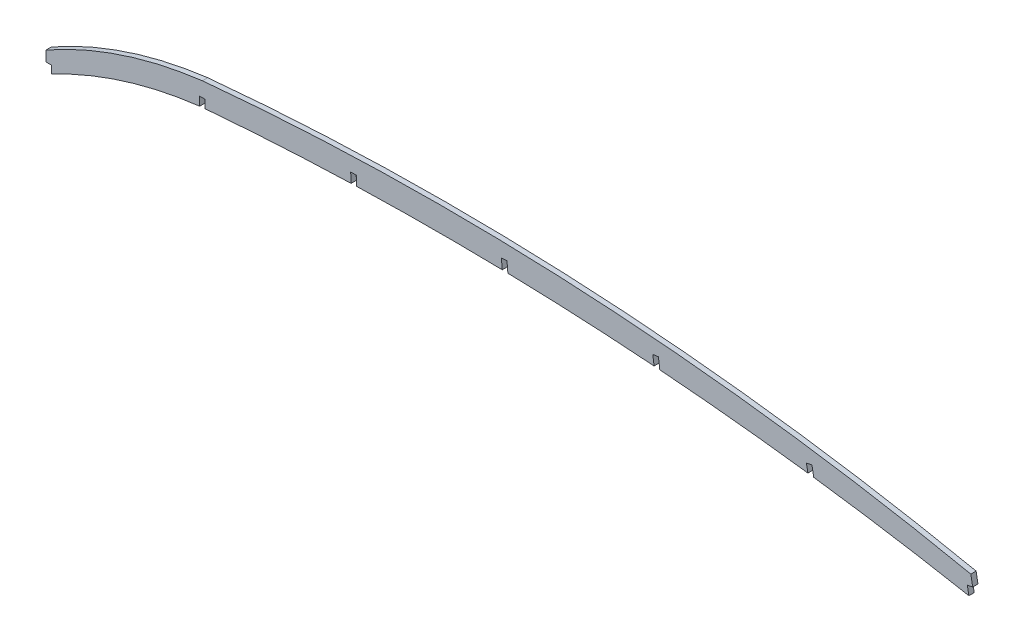
SolidWorks part; units mm, degrees
material "Balsa"
ref_plane "Front Plane" through (0, 0, 0) normal (0, 0, 1) x (1, 0, 0)
ref_plane "Top Plane" through (0, 0, 0) normal (0, 1, 0) x (1, 0, 0)
ref_plane "Right Plane" through (0, 0, 0) normal (1, 0, 0) x (0, 0, -1)
sketch "Sketch1" plane through (0, 0, 0) normal (0, 0, 1) x (1, 0, 0)
  line L2 (0, 0) -> (0, 169.3685) construction
  line L4 (93.98, 106.68) -> (556.5761, 106.68) construction
  line L9 (0, 106.68) -> (93.98, 106.68) construction
  line L14 (555.6382, 111.8229) -> (555.6382, 106.68) construction
  line L17 (555.6382, 111.8229) -> (557.917, 99.3265)
  line L19 (0, 106.68) -> (0, 93.98)
  line L20 (93.98, 137.668) -> (93.98, 123.7947) construction
  arc A6 (0, 106.68) -> (93.98, 137.668) centre (125.0054, -114.43) cw
  arc A8 (93.98, 137.668) -> (555.6382, 111.8229) centre (239.5165, -1398.7972) cw
  arc A9 (0, 93.98) -> (93.98, 123.7947) centre (122.3372, -128.6174) cw
  arc A25 (93.98, 123.7947) -> (557.917, 99.3265) centre (236.8486, -1577.8511) cw
  dimension "D4" = 254
  dimension "D2" = 93.98
  dimension "D8" = 1543.3426
  dimension "D9" = 100.334
  dimension "D3" = 30.988
  dimension "D12" = 254
  dimension "D14" = 1707.6328
  dimension "D1" = 106.68
  dimension "D5" = 462.5961
  dimension "D6" = 0.9378
  dimension "D7" = 5.1429
  dimension "D10" = 12.7025
  dimension "D11" = 12.7
  dimension "D13" = 13.8733
extrude "Boss-Extrude1" add sketch "Sketch1" along normal blind 3.175 contours A9 A25 L17 A8 A6 L19 region at (551.2665, 104.5698, 0)
sketch "Sketch2" plane through (0, 0, 3.175) normal (0, 0, 1) x (1, 0, 0)
  line L0 (0, 0) -> (0, 93.98) construction
  line L1 (0, 0) -> (93.98, 0) construction
  line L2 (93.98, 0) -> (93.98, 128.7725) construction
  line L3 (93.98, 0) -> (190.373, 0) construction
  line L4 (0, 93.98) -> (3.3528, 93.98)
  line L5 (0, 93.98) -> (0, 100.457)
  line L6 (0, 100.457) -> (3.3528, 100.457)
  line L7 (3.3528, 93.98) -> (3.3528, 100.457)
  line L8 (92.2909, 128.8487) -> (95.6691, 128.8487)
  line L9 (92.2909, 128.8487) -> (92.2909, 116.1487)
  line L10 (92.2909, 116.1487) -> (95.6691, 116.1487)
  line L11 (95.6691, 128.8487) -> (95.6691, 116.1487)
  line L12 (190.373, 0) -> (184.7454, 134.6815) construction
  line L13 (383.6414, 0) -> (367.0519, 124.8106) construction
  line L14 (367.0519, 124.8106) -> (366.2623, 130.7507) construction
  line L15 (183.0546, 134.6871) -> (186.4298, 134.8282)
  line L16 (183.0546, 134.6871) -> (183.5848, 121.9982)
  line L17 (186.4298, 134.8282) -> (186.96, 122.1393)
  line L18 (183.5848, 121.9982) -> (186.96, 122.1393)
  line L19 (480.4996, 0) -> (458.5303, 120.4774) construction
  line L20 (364.5779, 130.6037) -> (367.9267, 131.0488)
  line L21 (184.7454, 134.6815) -> (182.7802, 134.5994) construction
  line L22 (295.918, -122.9242) -> (299.0813, -122.6519)
  line L23 (276.8619, 135.4735) -> (273.6986, 135.2013)
  line L24 (298.5332, -116.2845) -> (295.3699, -116.5568)
  line L25 (274.2467, 128.8339) -> (277.41, 129.1062)
  line L26 (273.6986, 135.2013) -> (274.2467, 128.8339)
  line L27 (295.3699, -116.5568) -> (295.918, -122.9242)
  line L28 (276.8619, 135.4735) -> (277.41, 129.1062)
  line L29 (298.5332, -116.2845) -> (299.0813, -122.6519)
  line L30 (298.5332, -116.2845) -> (299.0813, -122.6519)
  line L32 (295.3699, -116.5568) -> (295.918, -122.9242)
  line L35 (298.5332, -116.2845) -> (295.3699, -116.5568)
  line L37 (295.918, -122.9242) -> (299.0813, -122.6519)
  line L38 (190.373, 0) -> (625.367, 0) construction
  line L39 (275.2802, 135.3374) -> (286.9301, 0) construction
  line L40 (364.5779, 130.6037) -> (365.8911, 120.7239)
  line L41 (273.5908, 135.2685) -> (276.9566, 135.5582)
  line L42 (273.5908, 135.2685) -> (274.68, 122.6152)
  line L43 (276.9566, 135.5582) -> (278.0458, 122.905)
  line L44 (274.68, 122.6152) -> (278.0458, 122.905)
  line L45 (367.9267, 131.0488) -> (369.2399, 121.169)
  line L46 (365.8911, 120.7239) -> (369.2399, 121.169)
  line L50 (456.855, 120.2494) -> (460.1784, 120.8554)
  line L53 (456.855, 120.2494) -> (458.4703, 111.3911)
  line L54 (460.1784, 120.8554) -> (461.7937, 111.9971)
  line L55 (458.4703, 111.3911) -> (461.7937, 111.9971)
  line L59 (574.4157, 0) -> (555.2161, 105.2887) construction
  line L60 (553.5407, 105.0607) -> (556.8641, 105.6667)
  line L61 (553.5407, 105.0607) -> (555.334, 95.2267)
  line L62 (556.8641, 105.6667) -> (558.6574, 95.8327)
  line L63 (555.334, 95.2267) -> (558.6574, 95.8327)
  point P20 (184.7422, 134.7577)
  point P31 (275.2737, 135.4133)
  point P36 (93.98, 128.8487)
  point P37 (366.2523, 130.8263)
  point P42 (458.5167, 120.5524)
  point P44 (555.2024, 105.3637)
  dimension "D1" = 93.98
  dimension "D2" = 6.477
  dimension "D3" = 3.3528
  dimension "D4" = 93.98
  dimension "D5" = 128.7725
  dimension "D6" = 3.3782
  dimension "D7" = 12.7
  dimension "D8" = 96.393
  dimension "D9" = 87.607
  dimension "D10" = 134.7991
  dimension "D11" = 0.0762
  dimension "D12" = 3.3782
  dimension "D13" = 85.08
  dimension "D14" = 96.5571
  dimension "D15" = 135.8379
  dimension "D16" = 0.0762
  dimension "D17" = 3.3782
  dimension "D18" = 12.7
  dimension "D19" = 12.7
  dimension "D20" = 0.0762
  dimension "D21" = 82.429
  dimension "D22" = 96.7113
  dimension "D23" = 125.9083
  dimension "D24" = 5.9924
  dimension "D25" = 0.0762
  dimension "D26" = 3.3782
  dimension "D27" = 79.666
  dimension "D28" = 96.8583
  dimension "D29" = 122.4641
  dimension "D30" = 3.3782
  dimension "D31" = 0.0762
  dimension "D32" = 79.666
  dimension "D33" = 93.9161
  dimension "D34" = 107.025
  dimension "D35" = 0.0762
  dimension "D36" = 3.3782
extrude "Cut-Extrude1" cut sketch "Sketch2" against normal through all
equation "\"slotwidth\"=0.167708"
